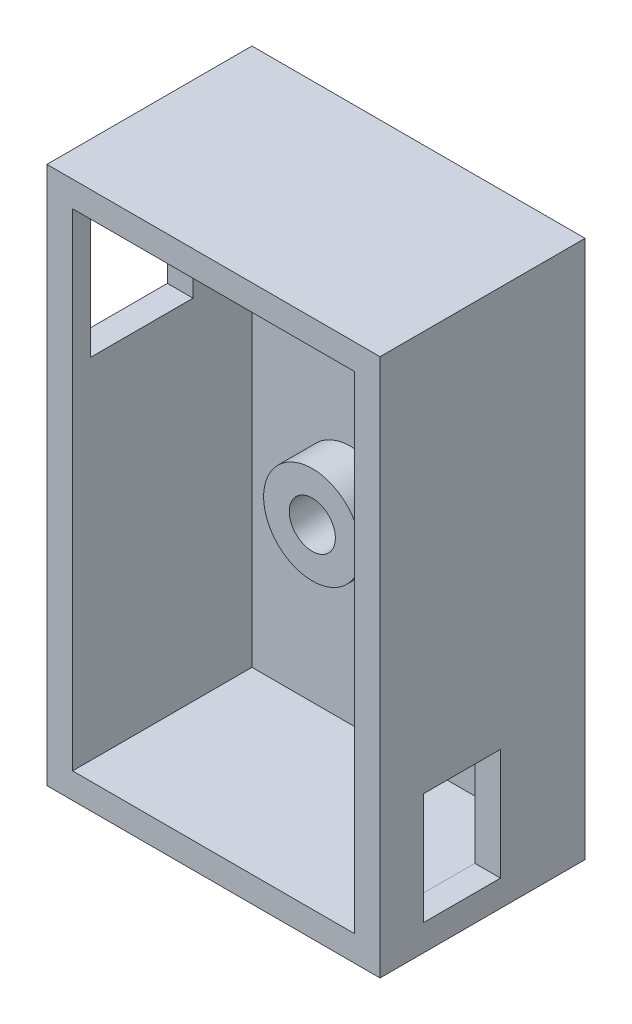
SolidWorks part; units mm, degrees
ref_plane "Front Plane" through (0, 0, 0) normal (0, 0, 1) x (1, 0, 0)
ref_plane "Top Plane" through (0, 0, 0) normal (0, 1, 0) x (1, 0, 0)
ref_plane "Right Plane" through (0, 0, 0) normal (1, 0, 0) x (0, 0, -1)
sketch "Sketch1" plane through (0, 0, 0) normal (0, 0, 1) x (1, 0, 0)
  line L1 (13, -21) -> (-13, -21)
  line L2 (13, -21) -> (13, 21)
  line L3 (13, 21) -> (-13, 21)
  line L4 (-13, -21) -> (-13, 21)
  line L5 (13, -21) -> (-13, 21) construction
  line L6 (13, 21) -> (-13, -21) construction
  point P0 (0, 0)
  dimension "D1" = 26
  dimension "D2" = 42
extrude "Boss-Extrude1" add sketch "Sketch1" along normal blind 16
shell "Shell1" thickness 2 removed face at (0, 0, 16)
sketch "Sketch2" plane through (0, 0, 2) normal (0, 0, 1) x (1, 0, 0)
  circle A0 centre (6.4862, 13.7354) radius 1.8
  circle A1 centre (-3.2882, -4.0064) radius 1.8
  circle A2 centre (-3.2882, -4.0064) radius 3.8
  circle A3 centre (6.4862, 13.7354) radius 3.8
  point P8 (0, 0)
  point P9 (0, 0)
  point P10 (6.4666, 13.7746)
  point P11 (6.4862, 13.7354)
  point P12 (-3.3715, -4.0089)
  point P13 (-3.3621, -3.9264)
  point P14 (-3.2882, -4.0163)
  point P15 (-3.2882, -4.0064)
  dimension "D1" = 2
  dimension "D2" = 2
extrude "Boss-Extrude2" add sketch "Sketch2" along normal blind 3
sketch "Sketch3" plane through (0, 0, 16) normal (0, 0, 1) x (1, 0, 0)
  line L0 (-13, 21) -> (-13, -21) construction
  line L1 (-11, 19) -> (-13, 19)
  line L2 (-11, 19) -> (-11, 8.2533)
  line L3 (-11, 8.2533) -> (-13, 8.2533)
  line L4 (-13, 19) -> (-13, 8.2533)
  line L5 (11, -19) -> (11, 19) construction
  line L6 (11, -10.159) -> (13, -10.159)
  line L7 (11, -10.159) -> (11, -19)
  line L8 (11, -19) -> (13, -19)
  line L9 (13, -10.159) -> (13, -19)
  line L10 (13, -21) -> (13, 21) construction
extrude "Cut-Extrude2" cut sketch "Sketch2<2>" against normal up to surface (2 mm away) contours A0 | A1 region at (6.4862, 13.7354, 2) region at (-3.2882, -4.0064, 2) up to face at (0, 0, 0)
sketch "Sketch2<2>" plane through (0, 0, 2) normal (0, 0, 1) x (1, 0, 0) same geometry as "Sketch2"
sketch "Sketch4" plane through (-13, 0, 0) normal (-1, 0, 0) x (0, 0, 1)
  line L1 (14.6, 18.9788) -> (6.6, 18.9788)
  line L2 (14.6, 18.9788) -> (14.6, 8.2533)
  line L3 (14.6, 8.2533) -> (6.6, 8.2533)
  line L4 (6.6, 18.9788) -> (6.6, 8.2533)
  line L5 (16, 21) -> (16, -21) construction
  dimension "D1" = 9.4
  dimension "D2" = 8
extrude "Cut-Extrude3" cut sketch "Sketch4" against normal up to surface (2 mm away) up to face at (-11, 0, 9)
sketch "Sketch5" plane through (13, 0, 0) normal (1, 0, 0) x (0, 0, -1)
  line L0 (-16, -21) -> (-16, 21) construction
  line L1 (-12.6, -10.2397) -> (-6.6, -10.2397)
  line L2 (-12.6, -10.2397) -> (-12.6, -18.9487)
  line L3 (-12.6, -18.9487) -> (-6.6, -18.9487)
  line L4 (-6.6, -10.2397) -> (-6.6, -18.9487)
  point P4 (-11.6, -18.9487)
  dimension "D1" = 9.4
  dimension "D2" = 6
extrude "Cut-Extrude4" cut sketch "Sketch5" against normal up to surface (2 mm away) up to face at (11, 0, 9)
